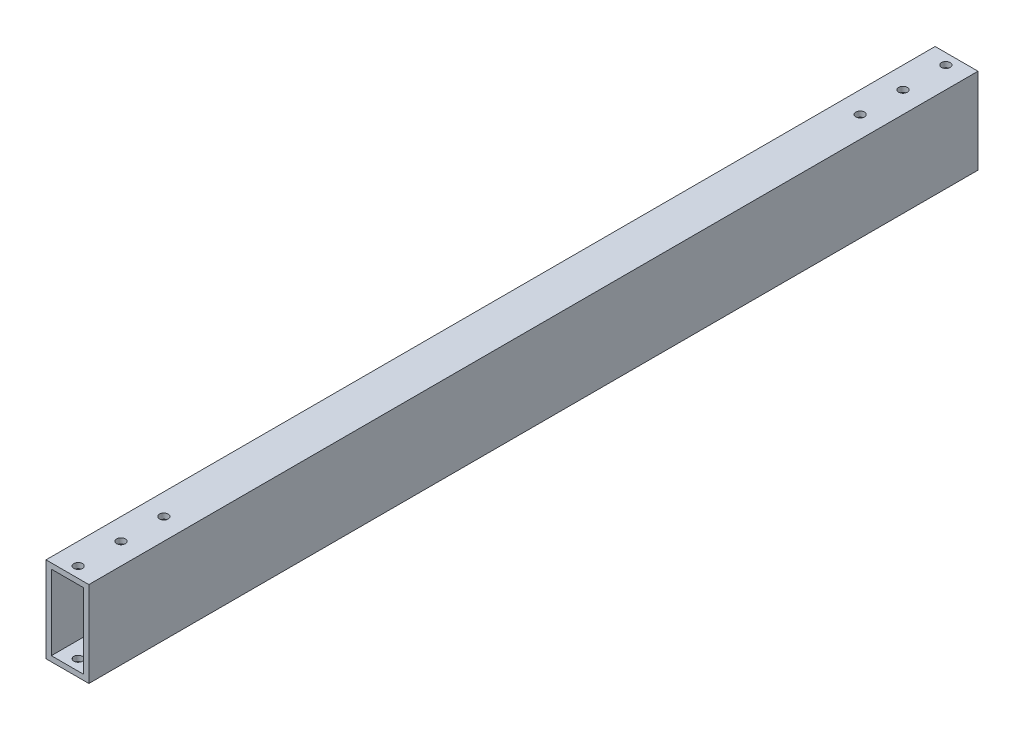
SolidWorks part; units mm, degrees
material "6061-T6 (SS)"
ref_plane "Front" through (0, 0, 0) normal (0, 0, 1) x (1, 0, 0)
ref_plane "Top" through (0, 0, 0) normal (0, 1, 0) x (1, 0, 0)
ref_plane "Right" through (0, 0, 0) normal (1, 0, 0) x (0, 0, -1)
sketch "Sketch1" plane through (0, 0, 0) normal (0, 0, 1) x (1, 0, 0)
  line L1 (-12.7, -25.4) -> (12.7, -25.4)
  line L2 (-12.7, -25.4) -> (-12.7, 25.4)
  line L3 (-12.7, 25.4) -> (12.7, 25.4)
  line L4 (12.7, -25.4) -> (12.7, 25.4)
  line L5 (-12.7, -25.4) -> (12.7, 25.4) construction
  line L6 (-12.7, 25.4) -> (12.7, -25.4) construction
  point P0 (0, 0)
  dimension "D1" = 25.4
  dimension "D2" = 50.8
extrude "Extrude-Thin1" add sketch "Sketch1" along normal blind 527.05 thin thin type one direction reverse wall 3.175
hole_wizard "#10 Clearance Hole1" positions "Sketch2" profile "Sketch3" hole size "#10" standard "ANSI Inch" end condition through all
sketch "Sketch2" plane through (0, 25.4, 0) normal (0, 1, 0) x (1, 0, 0)
  line L0 (12.7, -527.05) -> (-12.7, -527.05) construction
  line L1 (-12.7, -527.05) -> (-12.7, 0) construction
  point P0 (0, -520.7)
  point P2 (0, -495.3)
  point P4 (0, -469.9)
  point P6 (0, -6.35)
  point P8 (0, -31.75)
  point P10 (0, -57.15)
  dimension "D1" = 6.35
  dimension "D2" = 12.7
  dimension "D3" = 25.4
  dimension "D4" = 25.4
  dimension "D5" = 6.35
  dimension "D6" = 25.4
  dimension "D7" = 25.4
sketch "Sketch3" plane through (0, 25.4, 520.7) normal (1, 0, 0) x (0, 0, 1)
  line L0 (0, 0) -> (0, 50.8)
  line L1 (0, 50.8) -> (2.5527, 50.8)
  line L2 (2.5527, 50.8) -> (2.5527, 0)
  line L5 (2.5527, 0) -> (0, 0)
  line L11 (0, -6.35) -> (0, 107.95) construction
  dimension "Thru Hole Dia." = 5.1054
  dimension "Thru Hole Depth" = 50.8
sketch "Sketch6" plane through (0, -25.4, 0) normal (0, -1, 0) x (-1, 0, 0)
  point P0 (3.175, -70.358)
  point P3 (-3.175, -95.758)
  point P6 (3.175, -121.158)
  point P9 (-3.175, -146.558)
  point P12 (3.175, -171.958)
  point P15 (-3.175, -197.358)
  point P22 (-3.175, -248.158)
  point P25 (3.175, -273.558)
  point P28 (-3.175, -298.958)
  point P31 (3.175, -324.358)
  point P34 (-3.175, -349.758)
  point P37 (3.175, -375.158)
  point P40 (-3.175, -400.558)
  point P43 (3.175, -425.958)
  point P46 (-3.175, -451.358)
  point P54 (3.175, -222.758)
hole_wizard "1/8 (0.13) Diameter Hole1" positions "Sketch6" profile "Sketch5" hole size "1/8" standard "ANSI Inch" end condition up to next
sketch "Sketch5" plane through (-3.175, -25.4, 70.358) normal (1, 0, 0) x (0, 0, -1)
  line L0 (0, 0) -> (0, 3.175)
  line L1 (0, 3.175) -> (1.651, 3.175)
  line L2 (1.651, 3.175) -> (1.651, 0)
  line L5 (1.651, 0) -> (0, 0)
  line L11 (0, -6.35) -> (0, 107.95) construction
  dimension "Thru Hole Dia." = 3.302
  dimension "Thru Hole Depth" = 3.175
